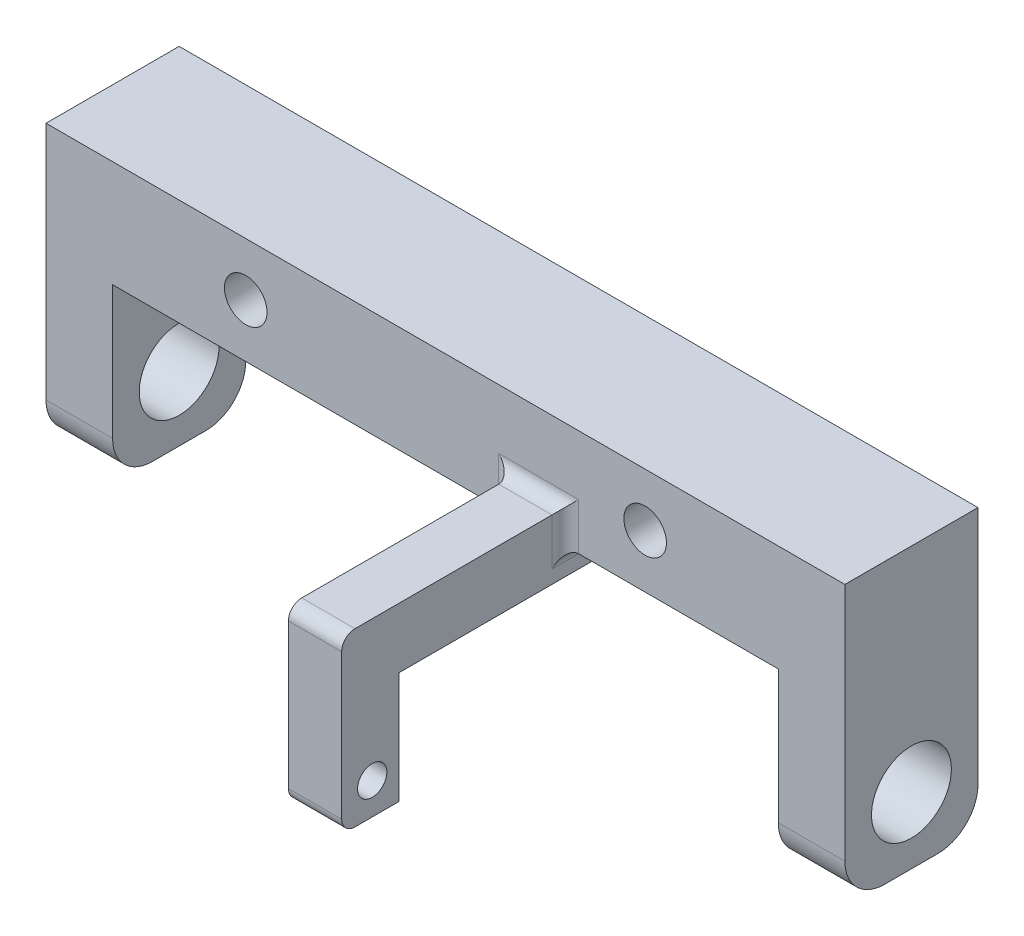
SolidWorks part; units mm, degrees
ref_plane "前视基准面" through (0, 0, 0) normal (0, 0, 1) x (1, 0, 0)
ref_plane "上视基准面" through (0, 0, 0) normal (0, 1, 0) x (1, 0, 0)
ref_plane "右视基准面" through (0, 0, 0) normal (1, 0, 0) x (0, 0, -1)
sketch "草图1" plane through (0, 0, 0) normal (0, 1, 0) x (1, 0, 0)
  line L1 (30, -5) -> (-30, -5)
  line L2 (30, -5) -> (30, 5)
  line L3 (30, 5) -> (-30, 5)
  line L4 (-30, -5) -> (-30, 5)
  line L5 (30, -5) -> (-30, 5) construction
  line L6 (30, 5) -> (-30, -5) construction
  point P0 (0, 0)
extrude "凸台-拉伸1" add sketch "草图1" along normal blind 8
sketch "草图2" plane through (30, 0, 0) normal (1, 0, 0) x (0, 0, -1)
  line L1 (-5, 8) -> (5, 8)
  line L2 (-5, 8) -> (-5, -13)
  line L3 (-5, -13) -> (5, -13)
  line L4 (5, 8) -> (5, -13)
  circle A0 centre (0, -8) radius 3
extrude "凸台-拉伸2" add sketch "草图2" against normal blind 5
mirror "镜向1" about plane through (0, 0, 0) normal (1, 0, 0) of "凸台-拉伸2"
fillet "圆角1" radius 3 4 edges at (-27.5, -13, -5) (-27.5, -13, 5) (27.5, -13, -5) (27.5, -13, 5)
ref_plane "基准面1" through (5, 0, 0) normal (-1, 0, 0) x (0, 0, 1)
sketch "草图3" plane through (5, 0, 0) normal (-1, 0, 0) x (0, 0, 1)
  line L0 (-8.5, -8) -> (-8.5, -2) construction
  line L1 (-6.5, -2) -> (17.5, -2)
  line L2 (-8.5, -8) -> (-6.5, -8) construction
  line L3 (-6.5, -8) -> (-6.5, -2)
  line L4 (-6.5, -8) -> (-6.5, -10.3764)
  line L5 (-6.5, -10.3764) -> (-10.8923, -10.3764)
  line L6 (-10.8923, -10.3764) -> (-10.8923, 2.5198)
  line L7 (-10.8923, 2.5198) -> (21.7929, 2.5198)
  line L8 (19.5, -8) -> (17.5, -8) construction
  line L9 (17.5, -8) -> (17.5, -2)
  line L10 (17.5, -8) -> (17.5, -10.3764)
  line L11 (17.5, -10.3764) -> (21.7929, -10.3764)
  line L12 (21.7929, -10.3764) -> (21.7929, 2.5198)
  circle A0 centre (0, -8) radius 3 construction
  circle A1 centre (0, -8) radius 3 construction
  circle A2 centre (-8.5, -8) radius 1.1
  circle A3 centre (19.5, -8) radius 1.1
  point P7 (-10.8923, 0)
extrude "凸台-拉伸3" add sketch "草图3" against normal blind 4
fillet "圆角4" radius 1 12 edges at (9, 0, 0) (5, 0, 0) (5, 1.2599, -5) (9, 1.2599, -5) (9, 1.2599, 5) (7, 2.5198, 21.7929) (7, -10.3764, 21.7929) (7, -10.3764, -10.8923) (7, 2.5198, -10.8923) (7, 2.5198, -5) (7, 2.5198, 5) (5, 1.2599, 5)
sketch "草图4" plane through (0, 0, 5) normal (0, 0, 1) x (1, 0, 0)
  circle A0 centre (-15, 4) radius 1.6
  circle A1 centre (15, 4) radius 1.6
extrude "切除-拉伸1" cut sketch "草图4" against normal through all both and the other way through all
